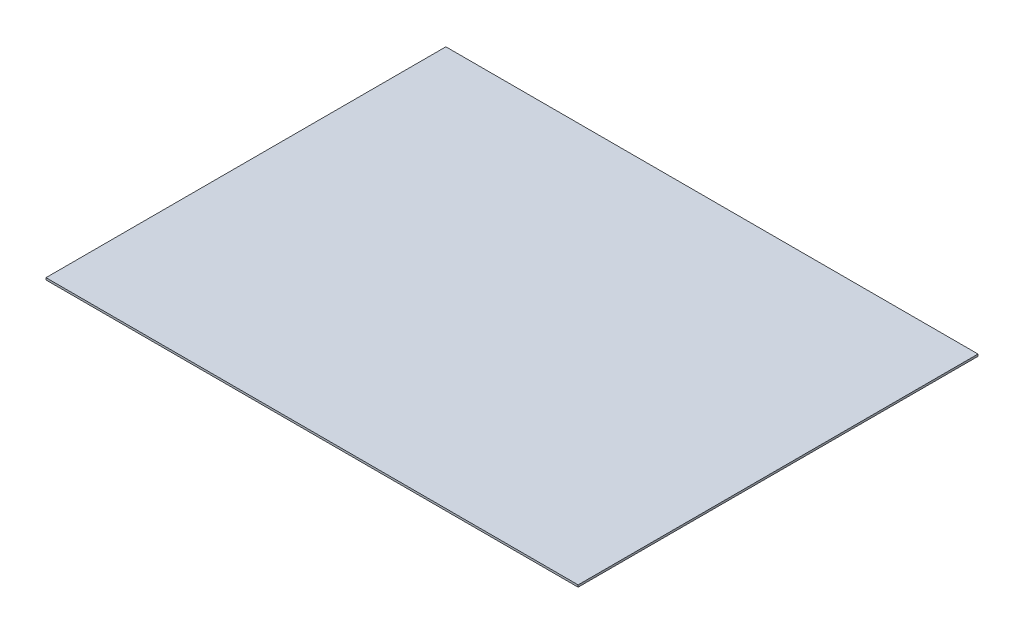
SolidWorks part; units mm, degrees
ref_plane "Front Plane" through (0, 0, 0) normal (0, 0, 1) x (1, 0, 0)
ref_plane "Top Plane" through (0, 0, 0) normal (0, 1, 0) x (1, 0, 0)
ref_plane "Right Plane" through (0, 0, 0) normal (1, 0, 0) x (0, 0, -1)
sketch "Sketch3" plane through (0, 0, 0) normal (0, 1, 0) x (1, 0, 0)
  line L1 (0, 0) -> (2615, 0)
  line L2 (0, 0) -> (0, 1965)
  line L3 (0, 1965) -> (2615, 1965)
  line L4 (2615, 0) -> (2615, 1965)
  dimension "D1" = 2615
  dimension "D2" = 1965
extrude "Boss-Extrude1" add sketch "Sketch3" along normal blind 10
